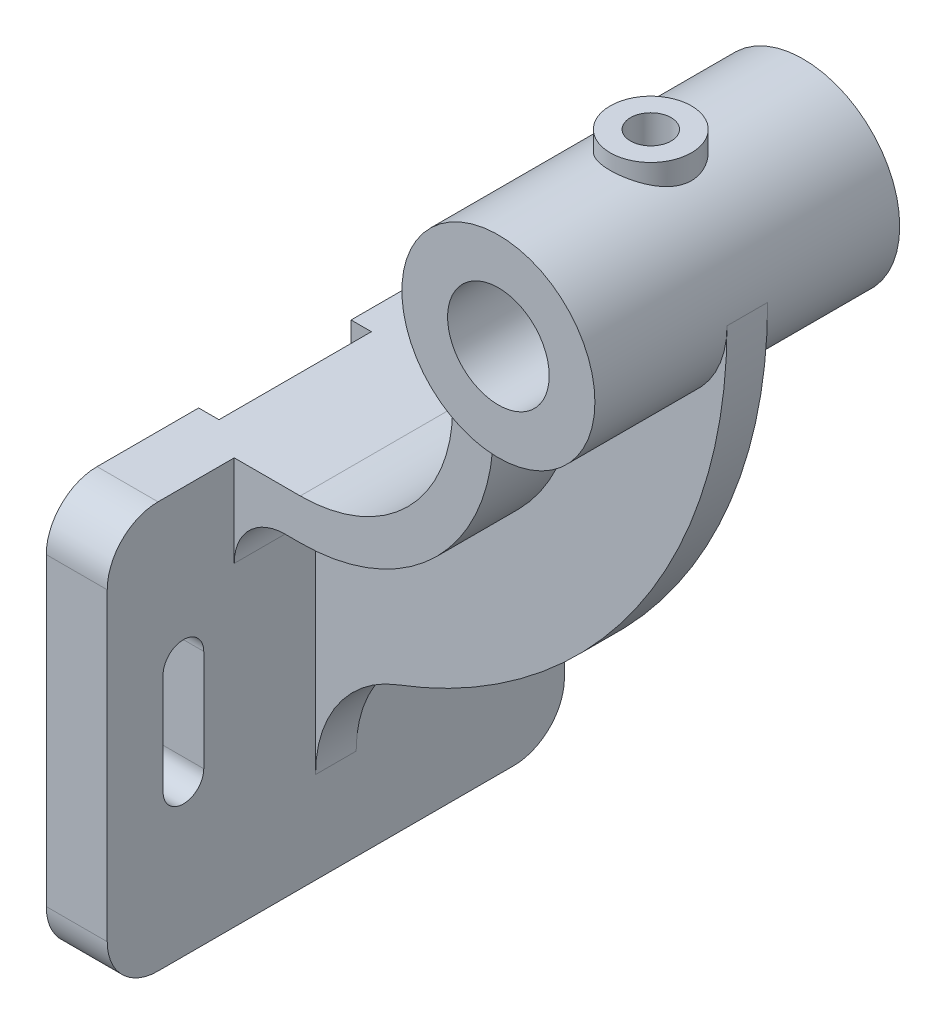
SolidWorks part; units mm, degrees
ref_plane "前视基准面" through (0, 0, 0) normal (0, 0, 1) x (1, 0, 0)
ref_plane "上视基准面" through (0, 0, 0) normal (0, 1, 0) x (1, 0, 0)
ref_plane "右视基准面" through (0, 0, 0) normal (1, 0, 0) x (0, 0, -1)
sketch "草图1" plane through (0, 0, 0) normal (0, 0, 1) x (1, 0, 0)
  circle A0 centre (0, 0) radius 19
  dimension "D1" = 38
extrude "凸台-拉伸1" add sketch "草图1" along normal mid plane 60
sketch "草图2" plane through (0, 0, 0) normal (0, 1, 0) x (1, 0, 0)
  circle A0 centre (0, 0) radius 8
  dimension "D1" = 16
extrude "凸台-拉伸2" add sketch "草图2" along normal blind 22
sketch "草图3" plane through (0, 0, 30) normal (0, 0, 1) x (1, 0, 0)
  circle A0 centre (0, 0) radius 10
  dimension "D1" = 20
extrude "切除-拉伸1" cut sketch "草图3" against normal through all
sketch "草图4" plane through (0, 22, 0) normal (0, 1, 0) x (1, 0, 0)
  circle A0 centre (0, 0) radius 4
  dimension "D1" = 8
extrude "切除-拉伸2" cut sketch "草图4" against normal up to next
sketch "草图5" plane through (0, 0, 0) normal (1, 0, 0) x (0, 0, -1)
  line L1 (-45, -135) -> (45, -135)
  line L2 (-45, -135) -> (-45, -55)
  line L3 (-45, -55) -> (45, -55)
  line L4 (45, -135) -> (45, -55)
  line L5 (-45, -135) -> (45, -55) construction
  line L6 (-45, -55) -> (45, -135) construction
  point P0 (0, -95)
  dimension "D1" = 90
  dimension "D2" = 80
  dimension "D3" = 95
extrude "凸台-拉伸3" add sketch "草图5" along normal blind 12 from offset 74 separate body offset against normal yes
fillet "圆角1" radius 10 4 edges at (-68, -135, -45) (-68, -135, 45) (-68, -55, -45) (-68, -55, 45)
sketch "草图6" plane through (-74, 0, 0) normal (-1, 0, 0) x (0, 0, 1)
  line L0 (-35, -55) -> (35, -55) construction
  line L1 (-15, -135) -> (15, -135)
  line L2 (-15, -135) -> (-15, -55)
  line L3 (-15, -55) -> (15, -55)
  line L4 (15, -135) -> (15, -55)
  line L5 (-15, -135) -> (15, -55) construction
  line L6 (-15, -55) -> (15, -135) construction
  line L7 (35, -135) -> (-35, -135) construction
  point P0 (0, -95)
  dimension "D1" = 30
extrude "切除-拉伸3" cut sketch "草图6" against normal blind 4
sketch "草图7" plane through (-62, 0, 0) normal (1, 0, 0) x (0, 0, -1)
  line L0 (-45, -95) -> (45, -95) construction
  line L1 (-45, -65) -> (-45, -125) construction
  line L2 (45, -125) -> (45, -65) construction
  line L3 (-30, -85) -> (-30, -105) construction
  line L4 (-26, -85) -> (-26, -105)
  line L5 (-34, -85) -> (-34, -105)
  arc A0 (-26, -85) -> (-34, -85) centre (-30, -85) ccw
  arc A1 (-34, -105) -> (-26, -105) centre (-30, -105) ccw
  point P8 (-30, -95)
  dimension "D1" = 8
  dimension "D2" = 20
  dimension "D3" = 30
extrude "切除-拉伸4" cut sketch "草图7" against normal through all
mirror "镜向1" about plane through (0, 0, 0) normal (0, 0, 1) of "切除-拉伸4"
sketch "草图8" plane through (0, 0, 0) normal (0, 0, 1) x (1, 0, 0)
  line L1 (-19, 0) -> (-19, -25)
  line L2 (-62, -55) -> (-49, -55)
  line L3 (-62, -117) -> (-62, -55)
  circle A0 centre (0, 0) radius 19 construction
  arc A1 (-19, 0) -> (19, 0) centre (0, 0) ccw
  arc A2 (-49, -55) -> (-19, -25) centre (-49, -25) ccw
  arc A3 (-45.8, -93.6) -> (19, 0) centre (-81, 0) ccw
  arc A4 (-45.8, -93.6) -> (-62, -117) centre (-37, -117) ccw
  dimension "D1" = 30
  dimension "D2" = 200
  dimension "D3" = 25
extrude "凸台-拉伸4" add sketch "草图8" along normal mid plane 8
sketch "草图9" plane through (0, 0, 0) normal (0, 0, 1) x (1, 0, 0)
  line L0 (-49, -55) -> (-62, -55) construction
  line L1 (-19, 0) -> (-19, -25) construction
  line L2 (-49, -55) -> (-62, -55)
  line L3 (-19, 0) -> (-19, -25)
  line L4 (-11, -15.4919) -> (-11, -25)
  line L5 (-49, -63) -> (-52, -63)
  line L6 (-11, 0) -> (-11, -25) construction
  line L9 (-49, -63) -> (-62, -63) construction
  line L11 (-62, -73) -> (-62, -55)
  arc A0 (-49, -55) -> (-19, -25) centre (-49, -25) ccw construction
  arc A1 (-49, -55) -> (-19, -25) centre (-49, -25) ccw
  arc A2 (-49, -63) -> (-11, -25) centre (-49, -25) ccw
  circle A3 centre (0, 0) radius 19 construction
  arc A5 (-62, -73) -> (-52, -63) centre (-52, -73) cw
  arc A6 (-19, 0) -> (-11, -15.4919) centre (0, 0) ccw
  point P12 (-11, -15.4919)
  dimension "D2" = 10
  dimension "D1" = 8
extrude "凸台-拉伸5" add sketch "草图9" along normal mid plane 40
fillet "圆角2" radius 10 2 edges at (-11, -15.4919, -12) (-11, -15.4919, 12)
